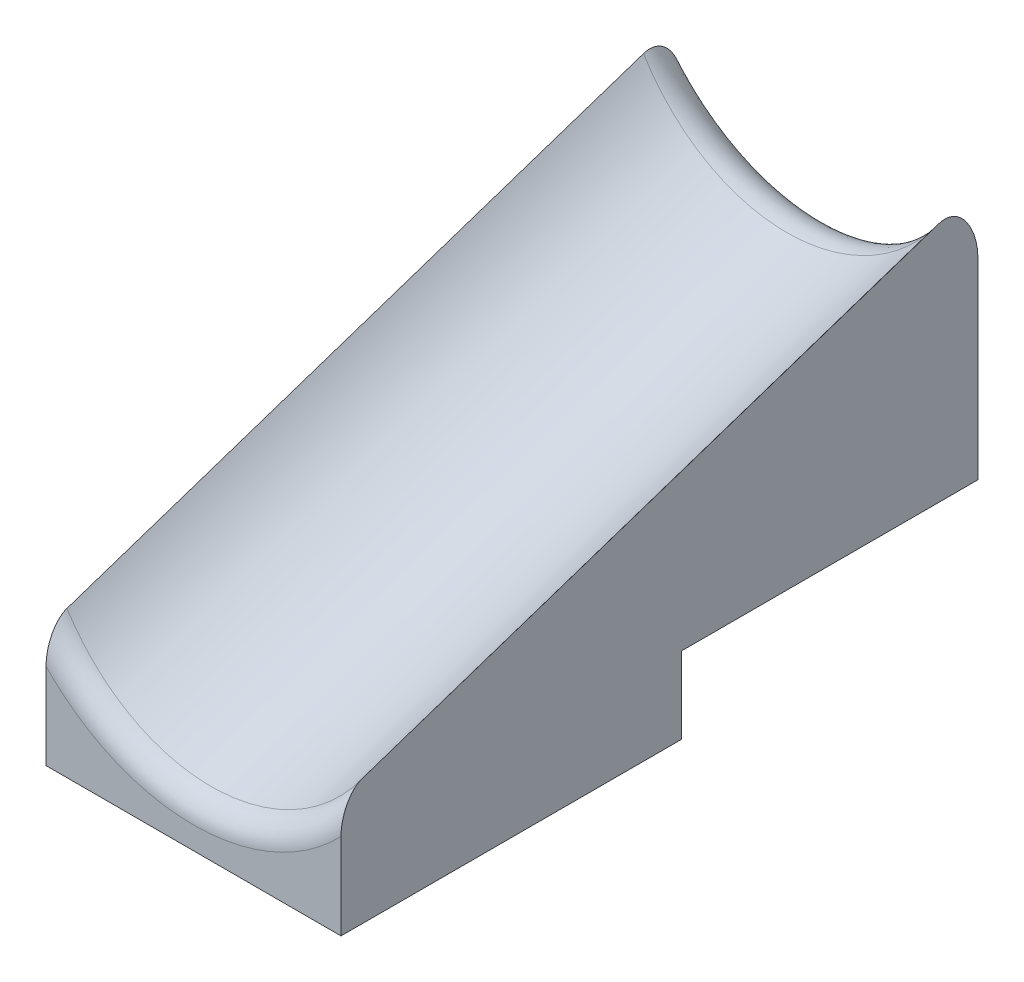
SolidWorks part; units mm, degrees
ref_plane "Front Plane" through (0, 0, 0) normal (0, 0, 1) x (1, 0, 0)
ref_plane "Top Plane" through (0, 0, 0) normal (0, 1, 0) x (1, 0, 0)
ref_plane "Right Plane" through (0, 0, 0) normal (1, 0, 0) x (0, 0, -1)
sketch "Sketch1" plane through (0, 0, 0) normal (0, 1, 0) x (1, 0, 0)
  line L1 (0, 0) -> (101.6, 0)
  line L2 (0, 0) -> (0, -304.8)
  line L3 (0, -304.8) -> (101.6, -304.8)
  line L4 (101.6, 0) -> (101.6, -304.8)
  dimension "D1" = 101.6
  dimension "D2" = 304.8
extrude "Boss-Extrude1" add sketch "Sketch1" along normal blind 101.6
sketch "Sketch3" plane through (101.6, 0, 0) normal (1, 0, 0) x (0, 0, -1)
  line L0 (-304.8, 0) -> (0, 101.6)
  line L1 (0, 101.6) -> (-304.8, 101.6)
  line L2 (-304.8, 101.6) -> (-304.8, 0)
extrude "Cut-Extrude1" cut sketch "Sketch3" against normal blind 101.6
ref_plane "Plane1" through (0, 10.16, -30.48) normal (0, 0.3162, -0.9487) x (-1, 0, 0)
sketch "Sketch4" plane through (0, 10.16, -30.48) normal (0, 0.3162, -0.9487) x (-1, 0, 0)
  line L2 (-101.6, 96.3862) -> (0, 96.3862) construction
  line L3 (0, 96.3862) -> (0, 0) construction
  circle A0 centre (-50.8, 134.4862) radius 63.5
  dimension "D1" = 127
  dimension "D2" = 38.1
  dimension "D3" = 50.8
extrude "Cut-Extrude2" cut sketch "Sketch4" against normal blind 508
sketch "Sketch7" plane through (101.6, 0, 0) normal (1, 0, 0) x (0, 0, -1)
  line L0 (-304.8, 0) -> (0, 0) construction
  line L1 (-21.79, 0) -> (-8.636, 0)
  line L2 (-21.79, 0) -> (-21.79, 13.97)
  line L3 (-21.79, 13.97) -> (-8.636, 13.97)
  line L4 (-8.636, 0) -> (-8.636, 13.97)
  line L5 (0, 101.6) -> (0, 0) construction
  dimension "D1" = 13.154
  dimension "D2" = 8.636
  dimension "D3" = 13.97
extrude "Cut-Extrude3" cut sketch "Sketch7" against normal blind 152.4
sketch "Sketch8" plane through (0, 0, 8.636) normal (0, 0, 1) x (1, 0, 0)
  line L0 (0, 0) -> (0, 13.97) construction
  line L1 (101.6, 0) -> (0, 0)
  line L2 (101.6, 0) -> (101.6, 6.985)
  line L3 (101.6, 6.985) -> (0, 6.985)
  line L4 (0, 0) -> (0, 6.985)
extrude "Boss-Extrude2" add sketch "Sketch8" along normal blind 6.35
chamfer "Chamfer1" distance 6.731 angle 60 1 edges at (50.8, 6.985, 14.986) first distance on face at (50.8, 6.985, 11.811)
sketch "Sketch9" plane through (0, 0, 0) normal (0, -1, 0) x (1, 0, 0)
  line L0 (101.6, 21.79) -> (0, 21.79)
  line L1 (101.6, 21.79) -> (101.6, 314.6167)
  line L2 (0, 21.79) -> (0, 314.6167)
  line L3 (101.6, 314.6167) -> (0, 314.6167)
  line L4 (0, 21.79) -> (101.6, 21.79) construction
extrude "Boss-Extrude3" add sketch "Sketch9" along normal blind 12.7
sketch "Sketch10" plane through (0, -12.7, 0) normal (0, -1, 0) x (-1, 0, 0)
  line L0 (-101.6, -314.6167) -> (0, -314.6167)
  line L1 (-101.6, -314.6167) -> (-101.6, -219.3667)
  line L2 (0, -314.6167) -> (0, -219.3667)
  line L3 (-101.6, -219.3667) -> (0, -219.3667)
  line L4 (-101.6, -21.79) -> (-101.6, -314.6167) construction
  line L5 (-101.6, -314.6167) -> (0, -314.6167) construction
  line L6 (0, -314.6167) -> (0, -21.79) construction
  dimension "D1" = 95.25
extrude "Cut-Extrude4" cut sketch "Sketch10" against normal blind 58.42
fillet "Fillet1" radius 8.89 1 edges at (50.8, 1.7038, 219.3667)
fillet "Fillet2" radius 11.43 1 edges at (50.8, 74.826, 0)
chamfer "Chamfer2" distance 0.3 angle 45 4 edges at (101.6, -12.7, 120.5783) (50.8, -12.7, 21.79) (0, -12.7, 120.5783) (50.8, -12.7, 219.3667)
sketch "Sketch11" plane through (101.6, 0, 0) normal (1, 0, 0) x (0, 0, -1)
  line L1 (0, 13.97) -> (-102.1, 13.97)
  line L2 (0, 13.97) -> (0, -24.13)
  line L3 (0, -24.13) -> (-102.1, -24.13)
  line L4 (-102.1, 13.97) -> (-102.1, -24.13)
  line L7 (-8.636, 13.97) -> (-21.79, 13.97) construction
  line L8 (0, 79.8909) -> (0, 0) construction
  dimension "D1" = 0
  dimension "D2" = 102.1
  dimension "D3" = 0
  dimension "D4" = 38.1
extrude "Cut-Extrude5" cut sketch "Sketch11" against normal blind 101.6
sketch "Sketch12" plane through (0, 13.97, 0) normal (0, -1, 0) x (1, 0, 0)
  line L0 (50.8, 0) -> (50.8, 102.1) construction
  line L1 (0, 0) -> (101.6, 0) construction
  line L2 (0, 102.1) -> (101.6, 102.1) construction
  circle A0 centre (50.8, 25.4) radius 19.05
  point P7 (50.8, 51.05)
  point P8 (50.8, 26.6433)
  point P9 (0, 0)
  dimension "D2" = 38.1
  dimension "D1" = 25.4
extrude "Boss-Extrude4" add sketch "Sketch12" along normal blind 25.4
